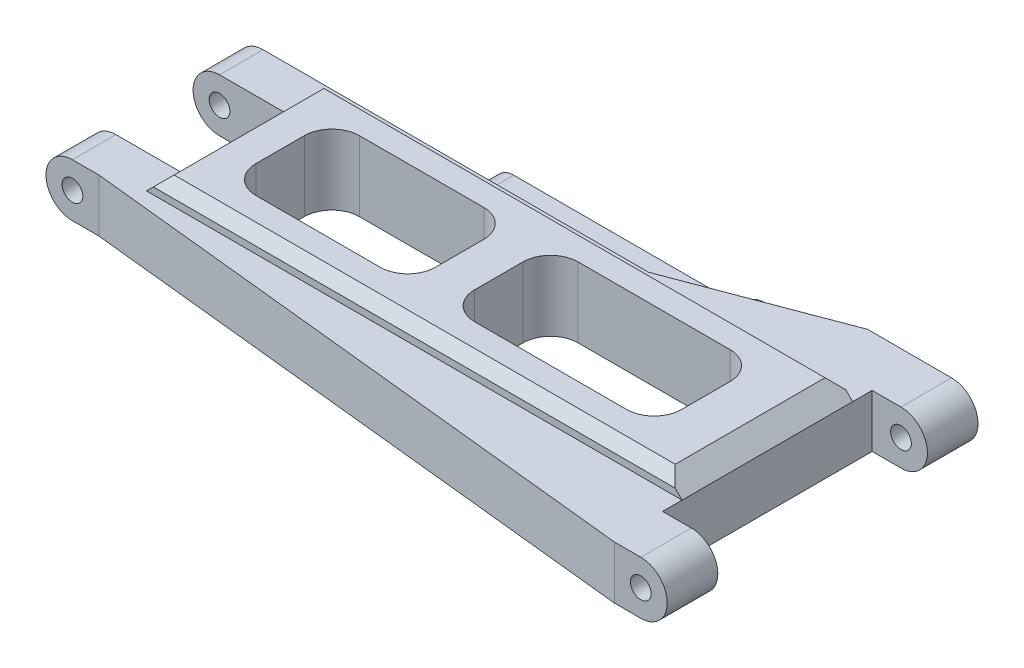
SolidWorks part; units mm, degrees
ref_plane "Front Plane" through (0, 0, 0) normal (0, 0, 1) x (1, 0, 0)
ref_plane "Top Plane" through (0, 0, 0) normal (0, 1, 0) x (1, 0, 0)
ref_plane "Right Plane" through (0, 0, 0) normal (1, 0, 0) x (0, 0, -1)
sketch "Sketch1" plane through (0, 0, 0) normal (0, 0, 1) x (1, 0, 0)
  line L0 (-45.5, 0) -> (45.5, 0) construction
  line L1 (-45.5, 3.83) -> (45.5, 3.83)
  line L2 (-45.5, -3.83) -> (45.5, -3.83)
  arc A0 (-45.5, 3.83) -> (-45.5, -3.83) centre (-45.5, 0) ccw
  arc A1 (45.5, -3.83) -> (45.5, 3.83) centre (45.5, 0) ccw
  circle A2 centre (-45.5, 0) radius 1.5
  circle A3 centre (45.5, 0) radius 1.5
  point P2 (0, 0)
  dimension "D3" = 3
  dimension "D1" = 7.66
  dimension "D2" = 91
extrude "Boss-Extrude1" add sketch "Sketch1" along normal mid plane 45
sketch "Sketch2" plane through (0, 3.83, 0) normal (0, 1, 0) x (1, 0, 0)
  line L0 (-41.67, -22.5) -> (41.67, -13.8)
  line L1 (45.5, -22.5) -> (-45.5, -22.5) construction
  line L2 (41.67, -13.8) -> (49.33, -13.8)
  line L3 (49.33, -22.5) -> (49.33, 22.5) construction
  line L4 (49.33, -13.8) -> (49.33, -22.5)
  line L5 (49.33, -22.5) -> (-41.67, -22.5)
  line L6 (-49.33, -22.5) -> (-45.5, -22.5) construction
  line L7 (-49.33, -22.5) -> (-45.5, -22.5)
  line L8 (-41.67, -22.5) -> (-45.5, -22.5)
  line L9 (45.5, -22.5) -> (49.33, -22.5) construction
  line L10 (45.5, -22.5) -> (49.33, -22.5)
  line L11 (45.5, -13.8) -> (41.67, -13.8)
  line L12 (-33.33, 22.5) -> (-10.33, 13.8)
  line L13 (45.5, 22.5) -> (-45.5, 22.5) construction
  line L14 (-10.33, 13.8) -> (49.33, 13.8)
  line L15 (49.33, 13.8) -> (49.33, 22.5)
  line L16 (49.33, 22.5) -> (-33.33, 22.5)
  line L17 (-49.33, 22.5) -> (-49.33, -22.5) construction
  line L19 (-6.43, 7.5) -> (-28.43, 7.5)
  line L20 (-2.43, 3.5) -> (-2.43, -3.5)
  line L21 (-6.43, -7.5) -> (-28.43, -7.5)
  line L22 (-32.43, 3.5) -> (-32.43, -3.5)
  line L23 (-2.43, 7.5) -> (-32.43, -7.5) construction
  line L24 (-2.43, -7.5) -> (-32.43, 7.5) construction
  line L25 (-41.33, -15.175) -> (-49.33, -15.175)
  line L26 (-41.33, -15.175) -> (-41.33, 15.175)
  line L27 (-41.33, 15.175) -> (-49.33, 15.175)
  line L28 (-49.33, -15.175) -> (-49.33, 15.175)
  line L29 (-41.33, -15.175) -> (-49.33, 15.175) construction
  line L30 (-41.33, 15.175) -> (-49.33, -15.175) construction
  line L31 (25.23, -7.5) -> (7.23, -7.5)
  line L32 (29.23, -3.5) -> (29.23, 3.5)
  line L33 (25.23, 7.5) -> (7.23, 7.5)
  line L34 (3.23, -3.5) -> (3.23, 3.5)
  line L35 (29.23, -7.5) -> (3.23, 7.5) construction
  line L36 (29.23, 7.5) -> (3.23, -7.5) construction
  line L37 (36.23, -7.5) -> (49.33, -7.5)
  line L38 (36.23, -7.5) -> (36.23, 7.5)
  line L39 (36.23, 7.5) -> (49.33, 7.5)
  line L40 (49.33, -7.5) -> (49.33, 7.5)
  line L41 (36.23, -7.5) -> (49.33, 7.5) construction
  line L42 (36.23, 7.5) -> (49.33, -7.5) construction
  arc A0 (-6.43, 7.5) -> (-2.43, 3.5) centre (-6.43, 3.5) cw
  arc A1 (-2.43, -3.5) -> (-6.43, -7.5) centre (-6.43, -3.5) cw
  arc A2 (-28.43, -7.5) -> (-32.43, -3.5) centre (-28.43, -3.5) cw
  arc A3 (-28.43, 7.5) -> (-32.43, 3.5) centre (-28.43, 3.5) ccw
  arc A4 (29.23, 3.5) -> (25.23, 7.5) centre (25.23, 3.5) ccw
  arc A5 (25.23, -7.5) -> (29.23, -3.5) centre (25.23, -3.5) ccw
  arc A6 (7.23, -7.5) -> (3.23, -3.5) centre (7.23, -3.5) cw
  arc A7 (7.23, 7.5) -> (3.23, 3.5) centre (7.23, 3.5) ccw
  point P23 (-17.43, 0)
  point P41 (-45.33, 0)
  point P47 (16.23, 0)
  point P62 (42.78, 0)
  line M11 (45.5, 22.5) -> (-45.5, 22.5)
  line M13 (-45.5, -22.5) -> (45.5, -22.5)
  line M14 (45.5, -22.5) -> (45.5, 22.5)
  dimension "D5" = 4
  dimension "D11" = 4
  dimension "D1" = 13.8
  dimension "D2" = 13.8
  dimension "D3" = 16
  dimension "D4" = 39
  dimension "D6" = 30
  dimension "D7" = 15
  dimension "D8" = 30.35
  dimension "D9" = 8
  dimension "D10" = 8.9
  dimension "D12" = 5.66
  dimension "D13" = 26
  dimension "D14" = 7
extrude "Cut-Extrude1" cut sketch "Sketch2" against normal through all contours L12 L14 M14 M11 | L2 L0 M13 M14 | L5 L4 L2 M14 | L15 L16 L14 M14 | L19 A3 L22 A2 L21 A1 L20 A0 | L33 A7 L34 A6 L31 A5 L32 A4 | L26 L27 L28 L25 | L37 L40 L39 L38 region at (11.5076, 3.83, -18.3977) region at (47.415, 3.83, -18.15) region at (16.3896, 3.83, 19.4779) region at (47.415, 3.83, 18.15) region at (-17.43, 3.83, 0) region at (16.23, 3.83, 0)
sketch "Sketch3" plane through (0, 0, 0) normal (0, 1, 0) x (1, 0, 0)
  line L0 (-41.33, -15.175) -> (-41.33, 15.175) construction
  line L1 (-41.33, -12.35) -> (36.23, -12.35)
  line L2 (-41.33, -12.35) -> (-41.33, 12.35)
  line L3 (-41.33, 12.35) -> (36.23, 12.35)
  line L4 (36.23, -12.35) -> (36.23, 12.35)
  line L5 (-41.33, -12.35) -> (36.23, 12.35) construction
  line L6 (-41.33, 12.35) -> (36.23, -12.35) construction
  line L7 (36.23, -7.5) -> (36.23, 7.5) construction
  line L13 (-6.43, 7.5) -> (-28.43, 7.5)
  line L14 (-2.43, -3.5) -> (-2.43, 3.5)
  line L15 (-28.43, -7.5) -> (-6.43, -7.5)
  line L16 (-32.43, 3.5) -> (-32.43, -3.5)
  line L17 (-6.43, 7.5) -> (-28.43, 7.5)
  line L18 (-2.43, -3.5) -> (-2.43, 3.5)
  line L19 (-28.43, -7.5) -> (-6.43, -7.5)
  line L20 (-32.43, 3.5) -> (-32.43, -3.5)
  line L21 (25.23, 7.5) -> (7.23, 7.5)
  line L22 (29.23, -3.5) -> (29.23, 3.5)
  line L23 (7.23, -7.5) -> (25.23, -7.5)
  line L24 (3.23, 3.5) -> (3.23, -3.5)
  line L25 (25.23, 7.5) -> (7.23, 7.5)
  line L26 (29.23, -3.5) -> (29.23, 3.5)
  line L27 (7.23, -7.5) -> (25.23, -7.5)
  line L28 (3.23, 3.5) -> (3.23, -3.5)
  arc A4 (-28.43, 7.5) -> (-32.43, 3.5) centre (-28.43, 3.5) ccw
  arc A5 (-2.43, 3.5) -> (-6.43, 7.5) centre (-6.43, 3.5) ccw
  arc A6 (-6.43, -7.5) -> (-2.43, -3.5) centre (-6.43, -3.5) ccw
  arc A7 (-32.43, -3.5) -> (-28.43, -7.5) centre (-28.43, -3.5) ccw
  arc A8 (-28.43, 7.5) -> (-32.43, 3.5) centre (-28.43, 3.5) ccw
  arc A9 (-2.43, 3.5) -> (-6.43, 7.5) centre (-6.43, 3.5) ccw
  arc A10 (-6.43, -7.5) -> (-2.43, -3.5) centre (-6.43, -3.5) ccw
  arc A11 (-32.43, -3.5) -> (-28.43, -7.5) centre (-28.43, -3.5) ccw
  arc A12 (7.23, 7.5) -> (3.23, 3.5) centre (7.23, 3.5) ccw
  arc A13 (29.23, 3.5) -> (25.23, 7.5) centre (25.23, 3.5) ccw
  arc A14 (25.23, -7.5) -> (29.23, -3.5) centre (25.23, -3.5) ccw
  arc A15 (3.23, -3.5) -> (7.23, -7.5) centre (7.23, -3.5) ccw
  arc A16 (7.23, 7.5) -> (3.23, 3.5) centre (7.23, 3.5) ccw
  arc A17 (29.23, 3.5) -> (25.23, 7.5) centre (25.23, 3.5) ccw
  arc A18 (25.23, -7.5) -> (29.23, -3.5) centre (25.23, -3.5) ccw
  arc A19 (3.23, -3.5) -> (7.23, -7.5) centre (7.23, -3.5) ccw
  point P0 (-2.55, 0)
  dimension "D1" = 24.7
  dimension "D2" = 0
  dimension "D3" = 0
extrude "Boss-Extrude2" add sketch "Sketch3" along normal offset from surface (6.33 mm away) 2.5 contours L1 L4 L3 L2 A19 L28 A16 L25 A17 L26 A18 L27 A11 L20 A8 L17 A9 L18 A10 L19 region at (-40.516, 0, 0) up to face at (-17.43, 3.83, 0) offset beyond the face yes
chamfer "Chamfer1" distance 2.5 angle 45 2 edges at (36.23, 6.33, 0) (-41.33, 6.33, 0)
chamfer "Chamfer2" distance 1.5 angle 45 2 edges at (-2.55, 6.33, -12.35) (-2.55, 6.33, 12.35)
sketch "Sketch4" plane through (0, 0, -13.8) normal (0, 0, -1) x (-1, 0, 0)
  line L0 (21.5, 0) -> (-12.5, 0) construction
  line L1 (21.5, -2.93) -> (-12.5, -2.93)
  line L2 (21.5, 2.93) -> (-12.5, 2.93)
  arc A0 (21.5, -2.93) -> (21.5, 2.93) centre (21.5, 0) ccw
  arc A1 (-12.5, 2.93) -> (-12.5, -2.93) centre (-12.5, 0) ccw
  point P2 (4.5, 0)
  point P10 (45.5, 0)
  dimension "D1" = 5.86
  dimension "D2" = 34
  dimension "D3" = 58
extrude "Boss-Extrude3" add sketch "Sketch4" along normal offset from surface (3.31 mm away) 4.76 up to face at (-2.55, 4.33, -12.35) offset beyond the face yes
sketch "Sketch5" plane through (0, 0, -17.11) normal (0, 0, -1) x (-1, 0, 0)
  circle A0 centre (21.5, 0) radius 3
  dimension "D1" = 6
extrude "Boss-Extrude4" add sketch "Sketch5" along normal blind 2.4
fillet "Fillet1" radius 0.5 1 edges at (-24.5, 0, -19.51)
sketch "Sketch6" plane through (0, 0, -19.51) normal (0, 0, -1) x (-1, 0, 0)
  line L0 (21.5, 0) -> (-12.5, 0) construction
  line L1 (-5.3, 0) -> (-12.5, 0) construction
  circle A0 centre (21.5, 0) radius 1.25
  circle A1 centre (9.1, 0) radius 1.25
  circle A2 centre (1.9, 0) radius 1.25
  circle A3 centre (-5.3, 0) radius 1.25
  circle A4 centre (-12.5, 0) radius 1.25
  circle A5 centre (-8.9, 0) radius 1.25
  dimension "D3" = 2.5
  dimension "D2" = 12.4
  dimension "D1" = 4
extrude "Cut-Extrude2" cut sketch "Sketch6" against normal blind 10
mirror "Mirror1" about plane through (0, 0, 0) normal (1, 0, 0) of bodies 106
delete or keep bodies "Body-Delete/Keep 1" type keep bodies bodies 107
